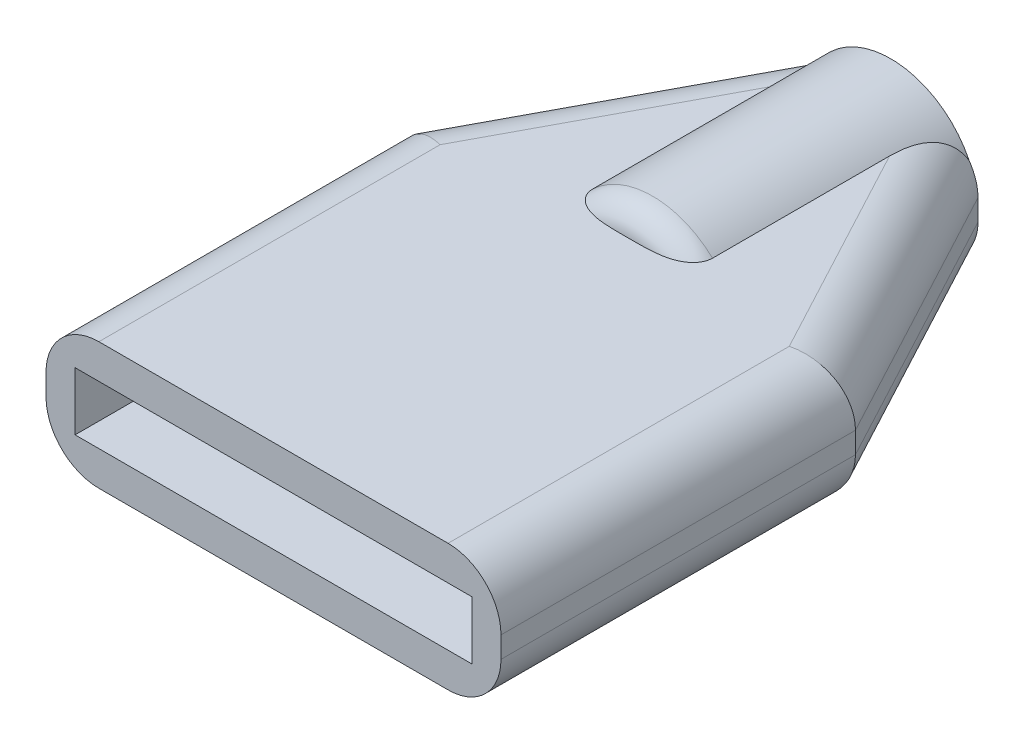
SolidWorks part; units mm, degrees
ref_plane "Front Plane" through (0, 0, 0) normal (0, 0, 1) x (1, 0, 0)
ref_plane "Top Plane" through (0, 0, 0) normal (0, 1, 0) x (1, 0, 0)
ref_plane "Right Plane" through (0, 0, 0) normal (1, 0, 0) x (0, 0, -1)
sketch "Sketch1" plane through (0, 0, 0) normal (0, 1, 0) x (1, 0, 0)
  line L1 (0, 0) -> (25.8, 0)
  line L2 (0, 0) -> (0, -35)
  line L3 (0, -35) -> (25.8, -35)
  line L4 (25.8, 0) -> (25.8, -35)
extrude "Boss-Extrude1" add sketch "Sketch1" along normal blind 7.2
sketch "Sketch2" plane through (0, 7.2, 0) normal (0, 1, 0) x (1, 0, 0)
  line L1 (0, -35) -> (1.9, -35)
  line L2 (0, -35) -> (25.8, -35) construction
sketch "Sketch3" plane through (0, 0, 35) normal (0, 0, 1) x (1, 0, 0)
  line L0 (0, 7.2) -> (1.65, 7.2)
  line L1 (0, 7.2) -> (25.8, 7.2) construction
  line L2 (1.65, 7.2) -> (1.65, 5.25)
  line L4 (1.65, 5.25) -> (24.15, 5.25)
  line L5 (1.65, 5.25) -> (1.65, 1.95)
  line L6 (1.65, 1.95) -> (24.15, 1.95)
  line L7 (24.15, 5.25) -> (24.15, 1.95)
extrude "Cut-Extrude1" cut sketch "Sketch3" against normal blind 20.5 contours L5 L4 L7 L6
sketch "Sketch4" plane through (0, 0, 14.5) normal (0, 0, 1) x (1, 0, 0)
  line L0 (12.9, 5.25) -> (12.9, 1.95)
  line L1 (1.65, 5.25) -> (24.15, 5.25) construction
  line L2 (1.65, 1.95) -> (24.15, 1.95) construction
  circle A0 centre (12.9, 3.6) radius 2.95
  point P8 (0, 0)
sketch "Sketch5" plane through (0, 0, 0) normal (0, 0, -1) x (-1, 0, 0)
  line L0 (-12.9, 7.2) -> (-12.9, 0)
  line L1 (-25.8, 7.2) -> (0, 7.2) construction
  line L2 (-25.8, 0) -> (0, 0) construction
  circle A0 centre (-12.9, 3.6) radius 4.95
  line M1 (-25.8, 0) -> (0, 0)
  line M3 (0, 7.2) -> (-25.8, 7.2)
extrude "Boss-Extrude2" add sketch "Sketch5" against normal blind 14.9 contours A0 M3 | A0 M1 region at (12.9, 7.7469, 0) region at (12.9, -0.5469, 0)
sketch "Sketch6" plane through (0, 0, 0) normal (0, 0, -1) x (-1, 0, 0)
  circle A0 centre (-12.9, 3.6) radius 2.95
extrude "Cut-Extrude3" cut sketch "Sketch6" against normal blind 13.5
fillet "Fillet1" radius 1.4 1 edges at (12.9, 8.55, 14.9)
fillet "Fillet2" radius 1.4 1 edges at (12.9, -1.35, 14.9)
sketch "Sketch7" plane through (0, 0, 0) normal (0, -1, 0) x (-1, 0, 0)
  line L0 (0, 0) -> (0, -14.9)
  line L1 (-12.9, 0) -> (-7.95, 0)
  line L2 (0, 0) -> (0, -35) construction
  line L3 (0, -14.9) -> (-7.95, 0)
  line L4 (-12.9, 0) -> (-12.9, -21.9159)
  line L6 (-25.8, 0) -> (-25.8, -14.9)
  line L7 (-25.8, -14.9) -> (-17.85, 0)
  line L8 (-7.95, 0) -> (0, 0)
  line L9 (-25.8, 0) -> (-17.85, 0)
  line M10 (-16.2974, 0) -> (-25.8, 0)
  line M11 (-25.8, 0) -> (-25.8, -35)
  line M13 (0, -35) -> (0, 0)
  line M14 (0, 0) -> (-9.5026, 0)
extrude "Cut-Extrude4" cut sketch "Sketch7" against normal blind 13.5 contours L7 M11 M10 | L3 M13 M14 region at (2.65, 0, 4.9667) region at (23.15, 0, 4.9667)
fillet "Fillet5" radius 3 8 edges at (25.8, 7.2, 24.95) (25.8, 0, 24.95) (21.825, 7.2, 7.45) (21.825, 0, 7.45) (0, 7.2, 24.95) (3.975, 7.2, 7.45) (3.975, 0, 7.45) (0, 0, 24.95)
